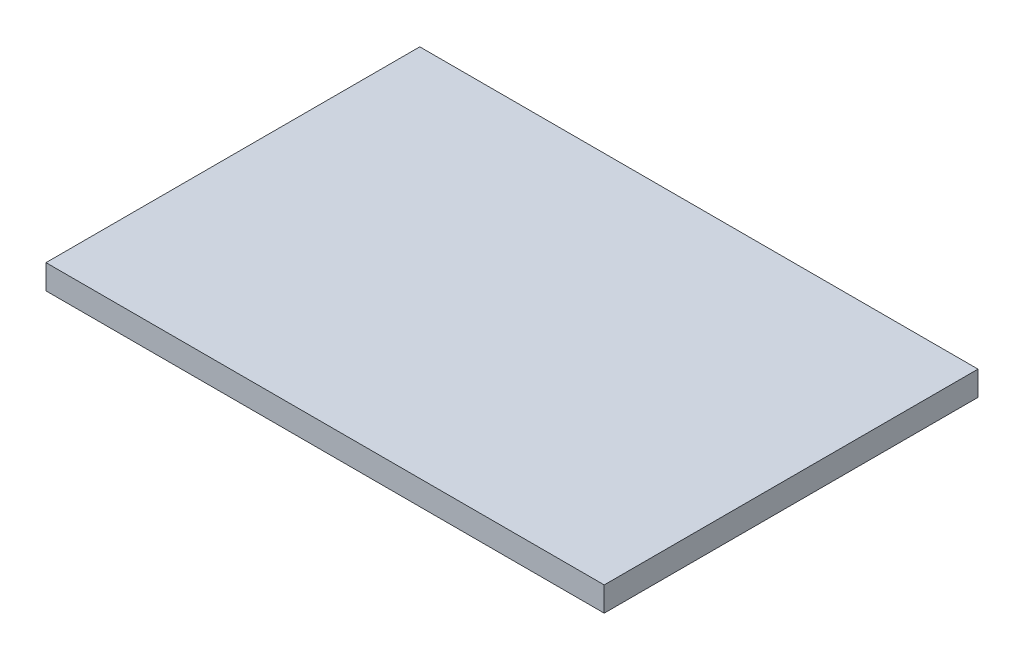
SolidWorks part; units mm, degrees
material "ABS"
ref_plane "Front Plane" through (0, 0, 0) normal (0, 0, 1) x (1, 0, 0)
ref_plane "Top Plane" through (0, 0, 0) normal (0, 1, 0) x (1, 0, 0)
ref_plane "Right Plane" through (0, 0, 0) normal (1, 0, 0) x (0, 0, -1)
sketch "Sketch1" plane through (0, 0, 0) normal (0, 1, 0) x (1, 0, 0)
  line L1 (-34.2, -22.9) -> (34.2, -22.9)
  line L2 (-34.2, -22.9) -> (-34.2, 22.9)
  line L3 (-34.2, 22.9) -> (34.2, 22.9)
  line L4 (34.2, -22.9) -> (34.2, 22.9)
  line L5 (-34.2, -22.9) -> (34.2, 22.9) construction
  line L6 (-34.2, 22.9) -> (34.2, -22.9) construction
  point P0 (0, 0)
  dimension "D1" = 45.8
  dimension "D2" = 68.4
extrude "Boss-Extrude1" add sketch "Sketch1" along normal blind 3
equation "\"smallPulleyTeeth\"= 30"
equation "\"largePulleyTeeth\"= 30"
equation "\"eighthThick\"= 3.0mm"
equation "\"sixteenthThick\"= 1.7mm"
equation "\"quarterThick\"=6.0mm"
equation "\"OD\"= 145mm"
equation "\"puckAngle\"= 60.5deg"
equation "\"puckDiam\"= 76.5mm"
equation "\"puckDist\"= 85mm"
equation "\"scoopFillet\"= 5mm"
equation "\"axlePress\"= 5.9mm"
equation "\"press\"= 0.2mm"
equation "\"wheelClear\"= 0.3mm"
equation "\"10-32clear\"= 4.8mm"
equation "\"10-32tap\"= 4.45mm"
equation "\"6-32clear\"= 3.3mm"
equation "\"8-32clear\"= 4.0mm"
equation "\"4-40clear\"= 3.0mm"
equation "\"wheelHeight\"= 22mm"
equation "\"wheelWell\"= 65mm"
equation "\"ledSmall\"= 3.1mm"
equation "\"ledLarge\"= 4.2mm"
equation "\"ledLength\"= 4.2mm"
equation "\"4-40close\"= 2.7mm"
equation "\"4-40nutThick\"= 2.2mm"
equation "\"4-40nutWidth\"= 6.2mm"
equation "\"4-40insertHeight\"= 3.5mm"
equation "\"4-40insert\"= 4mm"
equation "\"D1@Boss-Extrude1\"=\"eighthThick\""
